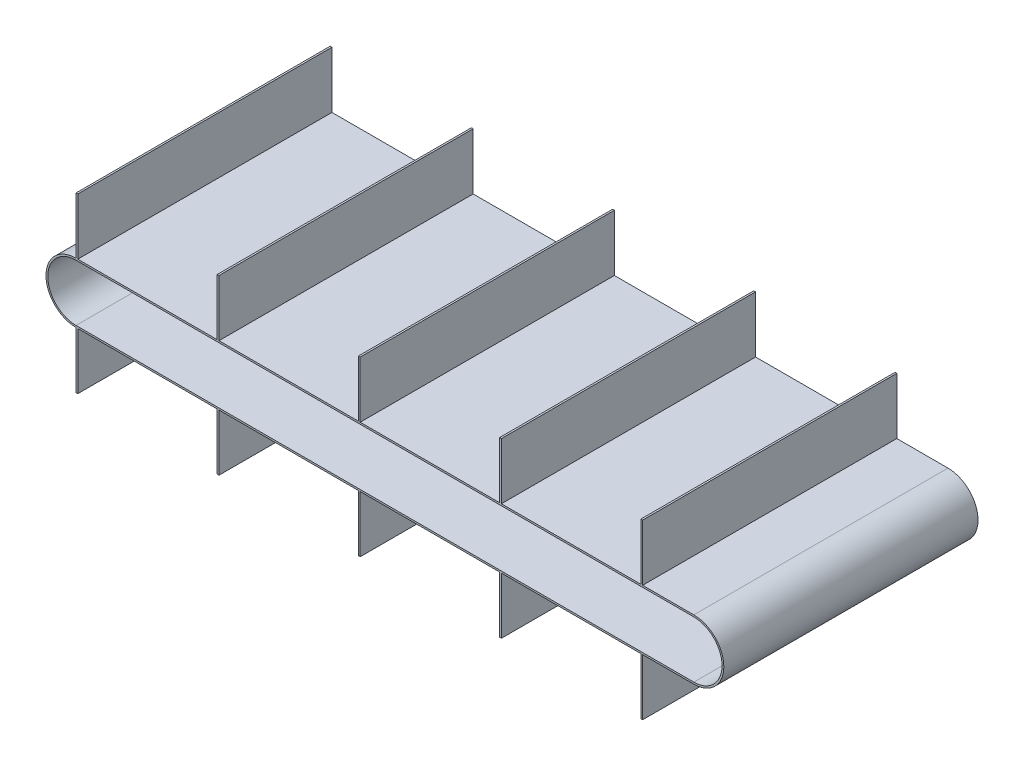
SolidWorks part; units mm, degrees
material "Silicon Rubber"
ref_plane "Front Plane" through (0, 0, 0) normal (0, 0, 1) x (1, 0, 0)
ref_plane "Top Plane" through (0, 0, 0) normal (0, 1, 0) x (1, 0, 0)
ref_plane "Right Plane" through (0, 0, 0) normal (1, 0, 0) x (0, 0, -1)
sketch "Sketch1" plane through (0, 0, 0) normal (0, 0, 1) x (1, 0, 0)
  line L0 (0, 26.9875) -> (555.625, 26.9875)
  line L1 (0, -26.9875) -> (555.625, -26.9875)
  arc A0 (0, 26.9875) -> (0, -26.9875) centre (0, 0) ccw
  arc A1 (555.625, -26.9875) -> (555.625, 26.9875) centre (555.625, 0) ccw
extrude "Boss-Extrude1" add sketch "Sketch1" against normal mid plane 228.6
sketch "Sketch3" plane through (0, 0, 114.3) normal (0, 0, 1) x (1, 0, 0)
  line L0 (0, 25.4) -> (555.625, 25.4)
  line L1 (0, -25.4) -> (555.625, -25.4)
  arc A0 (0, 25.4) -> (0, -25.4) centre (0, 0) ccw
  arc A1 (555.625, -25.4) -> (555.625, 25.4) centre (555.625, 0) ccw
extrude "Cut-Extrude1" cut sketch "Sketch3" against normal through all contours L0 A1 L1 A0
ref_plane "Plane1" through (0, -96.8375, 0) normal (0, -1, 0) x (-1, 0, 0)
sketch "Sketch4" plane through (0, 0, -114.3) normal (0, 0, -1) x (-1, 0, 0)
  line L1 (0, -26.9875) -> (-1.5875, -26.9875)
  line L2 (0, -26.9875) -> (0, -77.7875)
  line L3 (0, -77.7875) -> (-1.5875, -77.7875)
  line L4 (-1.5875, -26.9875) -> (-1.5875, -77.7875)
  dimension "D1" = 1.5875
  dimension "D2" = 50.8
extrude "Boss-Extrude2" add sketch "Sketch4" against normal up to surface (228.6 mm away) up to face at (277.8125, 0, 114.3)
pattern_linear "LPattern1" count 5 spacing 127 along (1, 0, 0) of "Boss-Extrude2"
mirror "Mirror1" about plane through (0, 0, 0) normal (0, 1, 0) of "LPattern1"
